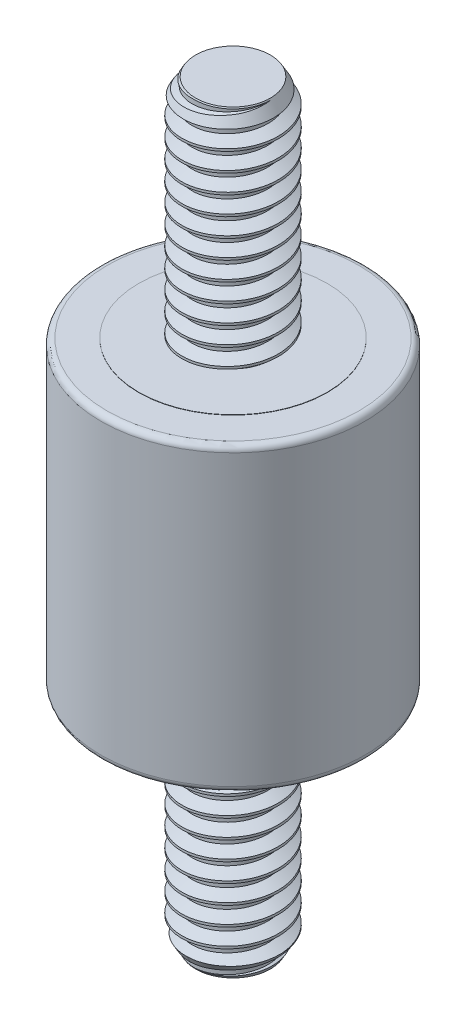
SolidWorks part; units mm, degrees
ref_plane "Front Plane" through (0, 0, 0) normal (0, 0, 1) x (1, 0, 0)
ref_plane "Top Plane" through (0, 0, 0) normal (0, 1, 0) x (1, 0, 0)
ref_plane "Right Plane" through (0, 0, 0) normal (1, 0, 0) x (0, 0, -1)
sketch "Sketch1" plane through (0, 0, 0) normal (0, 1, 0) x (1, 0, 0)
  circle A0 centre (0, 0) radius 5.5562
  dimension "D1" = 11.1125
extrude "Boss-Extrude1" add sketch "Sketch1" along normal mid plane 12.6746
sketch "Sketch2" plane through (0, 0, 0) normal (0, 1, 0) x (1, 0, 0)
  circle A0 centre (0, 0) radius 2.032
  dimension "D1" = 4.064
extrude "Boss-Extrude2" add sketch "Sketch2" along normal mid plane 31.75
sketch "Sketch9" plane through (0, 0, 0) normal (0, 1, 0) x (1, 0, 0)
  circle A0 centre (0, 0) radius 3.9688
  dimension "D1" = 7.9375
extrude "Boss-Extrude3" add sketch "Sketch9" along normal mid plane 12.7
chamfer "Chamfer1" distance 0.7937 angle 30 1 edges at (0, 15.875, 2.032) first distance on face at (0, 6.35, 2.032)
chamfer "Chamfer2" distance 0.7937 angle 30 1 edges at (0, -15.875, 2.032) first distance on face at (0, -15.875, 2.032)
thread "Thread1" pitch 0.7937 method cut trim with end face yes profile "Thread Profile1" start angle 0, offset 1.5875, length 0, pitch 0.7937, diameter 4.064
ref_plane "Plane1" through (-2.032, 16.6688, 0) normal (0, 0, 1) x (-1, 0, 0)
sketch "Thread Profile1" plane through (-2.032, 16.6688, 0) normal (0, 0, 1) x (-1, 0, 0)
  line L0 (0, 0) -> (0, 0.7937) construction
  line L11 (0, 0) -> (0, 0.6945)
  line L12 (0, 0.6945) -> (-0.4296, 0.4465)
  line L13 (-0.4296, 0.4465) -> (-0.4296, 0.248)
  line L15 (-0.4296, 0.248) -> (0, 0)
  line L17 (-0.4296, 0.3473) -> (0, 0.3473) construction
  point P2 (0, 0)
  dimension "Pitch" = 0.7937
  dimension "Profile_Angle" = 60
  dimension "Profile_Land" = 0.1984
  dimension "Profile_Height" = 0.4296
thread "Thread2" pitch 0.7937 method cut trim with end face yes profile "Thread Profile2" start angle 0, offset 1.5875, length 0, pitch 0.7937, diameter 4.064
ref_plane "Plane2" through (2.032, -16.6687, 0) normal (0, 0, 1) x (1, 0, 0)
sketch "Thread Profile2" plane through (2.032, -16.6687, 0) normal (0, 0, 1) x (1, 0, 0)
  line L0 (0, 0) -> (0, 0.7937) construction
  line L11 (0, 0) -> (0, 0.6945)
  line L12 (0, 0.6945) -> (-0.4296, 0.4465)
  line L13 (-0.4296, 0.4465) -> (-0.4296, 0.248)
  line L15 (-0.4296, 0.248) -> (0, 0)
  line L17 (-0.4296, 0.3473) -> (0, 0.3473) construction
  point P2 (0, 0)
  dimension "Pitch" = 0.7937
  dimension "Profile_Angle" = 60
  dimension "Profile_Land" = 0.1984
  dimension "Profile_Height" = 0.4296
fillet "Fillet1" radius 0.254 2 edges at (0, 6.3373, 5.5562) (0, -6.3373, 5.5562)
